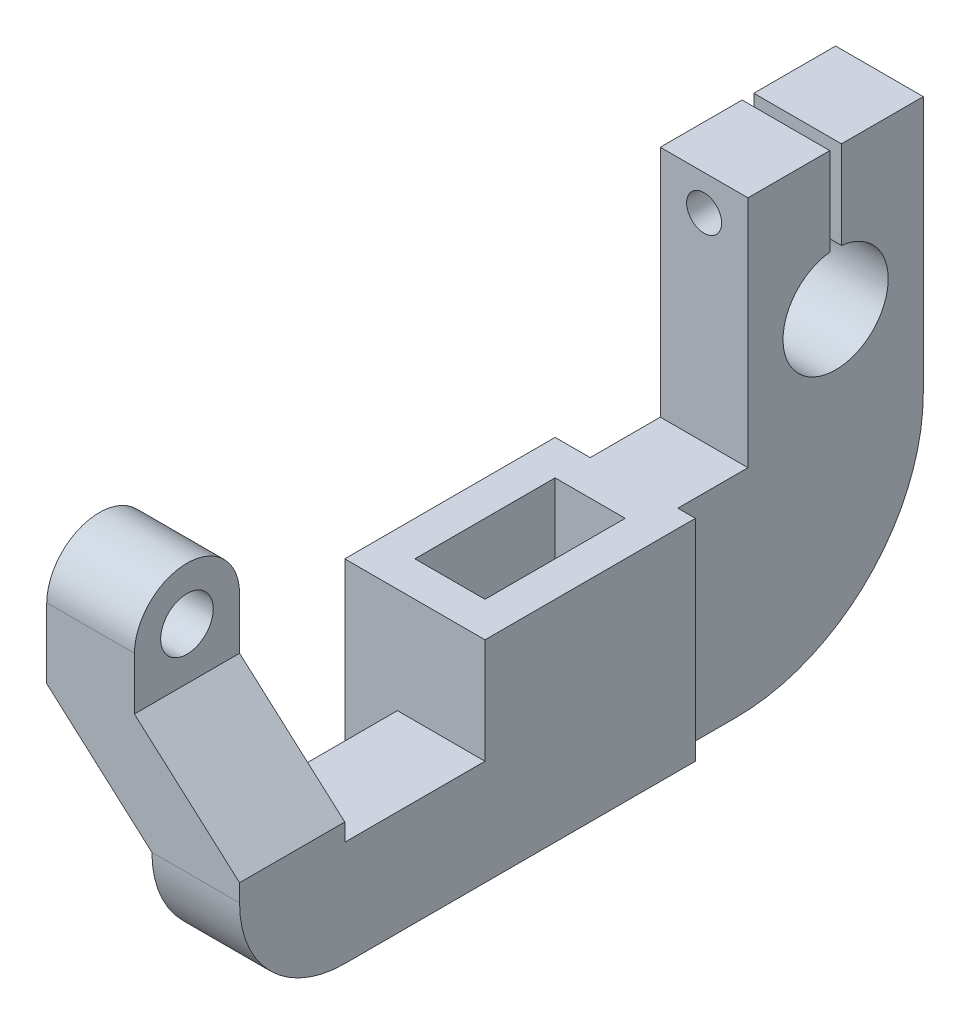
SolidWorks part; units mm, degrees
ref_plane "Front Plane" through (0, 0, 0) normal (0, 0, 1) x (1, 0, 0)
ref_plane "Top Plane" through (0, 0, 0) normal (0, 1, 0) x (1, 0, 0)
ref_plane "Right Plane" through (0, 0, 0) normal (1, 0, 0) x (0, 0, -1)
sketch "Sketch1" plane through (0, 0, 0) normal (1, 0, 0) x (0, 0, -1)
  line L0 (0, 0) -> (30, 0)
  line L1 (30, 0) -> (30, -44)
  line L2 (-2, -76) -> (-12, -76)
  line L3 (0, 0) -> (0, -40)
  line L4 (0, -40) -> (-48, -40)
  line L5 (-12, -76) -> (-48, -76)
  line L6 (-48, -40) -> (-48, -58)
  line L7 (-48, -58) -> (-72, -58)
  line L8 (-48, -76) -> (-72, -76)
  line L9 (-72, -58) -> (-72, -30)
  line L11 (-90, -30) -> (-90, -58)
  line L12 (15, 0) -> (15, -15) construction
  line L13 (14, 0) -> (14, -15.0557)
  line L14 (16, 0) -> (16, -15.0557)
  line L15 (14, 0) -> (14, -19.9038) construction
  line L16 (15, 0) -> (15, -19.9038) construction
  line L17 (16, 0) -> (16, -19.9038) construction
  line L18 (-90, -39.1388) -> (-72, -39.1388)
  line L19 (-72, -55.1388) -> (-90, -55.1388)
  arc A0 (14, -15.0557) -> (16, -15.0557) centre (15, -24) ccw
  arc A1 (-72, -30) -> (-90, -30) centre (-81, -30.1388) ccw
  circle A2 centre (-81, -30.1388) radius 4.5
  arc A3 (30, -44) -> (-2, -76) centre (-2, -44) cw
  arc A5 (-90, -58) -> (-72, -76) centre (-72, -58) ccw
  point P15 (15, 0)
  point P32 (30, -76)
  dimension "D12" = 24
  dimension "D13" = 18
  dimension "D16" = 9
  dimension "D19" = 32
  dimension "D20" = 18
  dimension "D1" = 30
  dimension "D2" = 76
  dimension "D3" = 42
  dimension "D4" = 40
  dimension "D5" = 48
  dimension "D6" = 36
  dimension "D7" = 18
  dimension "D8" = 24
  dimension "D9" = 18
  dimension "D10" = 28
  dimension "D11" = 18
  dimension "D14" = 1
  dimension "D17" = 9
  dimension "D18" = 16
  dimension "D15" = 1
extrude "Boss-Extrude2" add sketch "Sketch1" against normal blind 33 contours L4 L6 L7 L9 A1 L11 A5 L8 L5 L2 A3 L1 L0 L3
extrude "Cut-Extrude1" cut sketch "Sketch1<4>" against normal through all both and the other way through all contours L13 A0 L14 L0 region at (0, -22.259, -15)
sketch "Sketch1<4>" plane through (0, 0, 0) normal (1, 0, 0) x (0, 0, -1) same geometry as "Sketch1"
extrude "Cut-Extrude2" cut sketch "Sketch1<5>" against normal through all both and the other way through all contours A2 region at (0, -30.1388, 81)
sketch "Sketch1<5>" plane through (0, 0, 0) normal (1, 0, 0) x (0, 0, -1) same geometry as "Sketch1"
sketch "Sketch3" plane through (0, 0, 0) normal (0, 1, 0) x (1, 0, 0)
  line L0 (-33, -48) -> (0, -48) construction
  line L1 (-33, 0) -> (-24, 0)
  line L2 (-33, 0) -> (-33, -48)
  line L3 (-33, -48) -> (-24, -48)
  line L4 (-24, 0) -> (-24, -48)
  dimension "D1" = 9
extrude "Cut-Extrude3" cut sketch "Sketch3" against normal through all both and the other way through all contours L2 L1 L4 L3
sketch "Sketch4" plane through (0, -58, 0) normal (0, 1, 0) x (1, 0, 0)
  line L0 (-33, -72) -> (0, -72) construction
  line L1 (-33, -48) -> (-15, -48)
  line L2 (-33, -48) -> (-33, -72)
  line L3 (-33, -72) -> (-15, -72)
  line L4 (-15, -48) -> (-15, -72)
  dimension "D1" = 18
extrude "Cut-Extrude4" cut sketch "Sketch4" against normal through all both and the other way through all
sketch "Sketch5" plane through (0, -40, 0) normal (0, 1, 0) x (1, 0, 0)
  line L1 (-33, 30) -> (-24, 30)
  line L2 (-33, 30) -> (-33, 0)
  line L3 (-33, 0) -> (-24, 0)
  line L4 (-24, 30) -> (-24, 0)
extrude "Cut-Extrude5" cut sketch "Sketch5" against normal through all both and the other way through all
sketch "Sketch6" plane through (0, -40, 0) normal (0, 1, 0) x (1, 0, 0)
  line L0 (-24, -48) -> (-24, -12)
  line L1 (-24, 0) -> (-24, -48) construction
  line L2 (-24, 30) -> (0, 30) construction
  line L3 (-24, -12) -> (-18, -12)
  line L4 (-24, -12) -> (-24, 30)
  line L5 (-24, 30) -> (-18, 30)
  line L6 (-18, -12) -> (-18, 30)
  line M3 (0, 0) -> (-24, 0)
  line M4 (-24, 0) -> (-24, -48)
  dimension "D1" = 36
  dimension "D2" = 6
extrude "Cut-Extrude6" cut sketch "Sketch6" against normal through all both and the other way through all contours L6 L5 L4 M3 | L3 L6 M3 M4 region at (-21, -40, 6) region at (-21, -40, -15)
sketch "Sketch7" plane through (0, -40, 0) normal (0, 1, 0) x (1, 0, 0)
  line L0 (-18, -12) -> (-3, -12)
  line L2 (-3, -12) -> (10.7135, -12)
  line L3 (-3, -12) -> (-3, 35.2512)
  line L4 (-3, 35.2512) -> (10.7135, 35.2512)
  line L5 (10.7135, -12) -> (10.7135, 35.2512)
  line M6 (0, -48) -> (0, 0)
  line M7 (0, 0) -> (-18, 0)
  dimension "D1" = 15
extrude "Cut-Extrude7" cut sketch "Sketch7" against normal through all both and the other way through all contours L2 L5 L4 L3 M7 M6 | L3 L2 M6 M7 region at (-1.5, -40, 6) region at (4.1718, -40, -12.6624)
sketch "Sketch8" plane through (0, -40, 0) normal (0, 1, 0) x (1, 0, 0)
  line L0 (-24, -12) -> (-24, -48) construction
  line L1 (-18, -42) -> (-6, -42)
  line L2 (-18, -42) -> (-18, -18)
  line L3 (-18, -18) -> (-6, -18)
  line L4 (-6, -42) -> (-6, -18)
  line L5 (0, -12) -> (0, -48) construction
  line L6 (-24, -48) -> (0, -48) construction
  line L7 (-24, -12) -> (-18, -12) construction
  dimension "D1" = 6
  dimension "D2" = 6
  dimension "D3" = 6
  dimension "D4" = 6
extrude "Cut-Extrude8" cut sketch "Sketch8" against normal through all both and the other way through all
sketch "Sketch9" plane through (0, 0, 0) normal (0, 0, 1) x (1, 0, 0)
  line L0 (-18, 0) -> (-3, 0) construction
  circle A0 centre (-10.5, -6) radius 3
  point P4 (0, 0)
  point P5 (-10.5, 0)
  dimension "D1" = 6
  dimension "D2" = 6
extrude "Cut-Extrude10" cut sketch "Sketch9" against normal up to next
sketch "Sketch10" plane through (0, 0, 90) normal (0, 0, 1) x (1, 0, 0)
  line L2 (-33, -30) -> (-33, -42)
  line L3 (-33, -30) -> (-33, -58) construction
  line L4 (0, -76) -> (-15, -76)
  line L5 (-33, -42) -> (-15, -58)
  line L6 (-15, -58) -> (-15, -76)
  line L7 (-15, -76) -> (-33, -76)
  line L8 (-33, -58) -> (-33, -76) construction
  line L9 (-33, -76) -> (-15, -76) construction
  line L10 (-33, -76) -> (-33, -42)
  line M6 (-33, -30) -> (-33, -58)
  line M7 (-33, -58) -> (0, -58)
  dimension "D1" = 12
  dimension "D2" = 15
  dimension "D3" = 16
extrude "Cut-Extrude11" cut sketch "Sketch10" against normal blind 27 contours L10 L7 L6 M7 | L5 M6 M7 region at (-27, -52.6667, 90) region at (-24, -67, 90)
sketch "Sketch11" plane through (0, 0, 90) normal (0, 0, 1) x (1, 0, 0)
  line L0 (-33, -21.1378) -> (-18, -21.1378)
  line L1 (0, -21.1378) -> (-33, -21.1378) construction
  line L6 (-18, -30) -> (-18, -39)
  line L7 (-33, -30) -> (0, -30) construction
  line L8 (-18, -40) -> (-18, 0) construction
  line L9 (-18, -39) -> (0, -55)
  line L10 (-33, -42) -> (-15, -58) construction
  line L11 (-18, -30) -> (-18, -21.1378)
  line L12 (0, -21.1378) -> (0, -55)
  line L13 (-18, -21.1378) -> (0, -21.1378)
  line M8 (0, -58) -> (0, -30)
  line M9 (0, -30) -> (-33, -30)
  dimension "D1" = 15
  dimension "D2" = 9
  dimension "D3" = 16
extrude "Cut-Extrude12" cut sketch "Sketch11" against normal blind 27 contours L13 L11 L12 M9 | L6 L9 M8 M9 region at (-7.5882, -39.1275, 90) region at (-9, -25.5689, 90)
